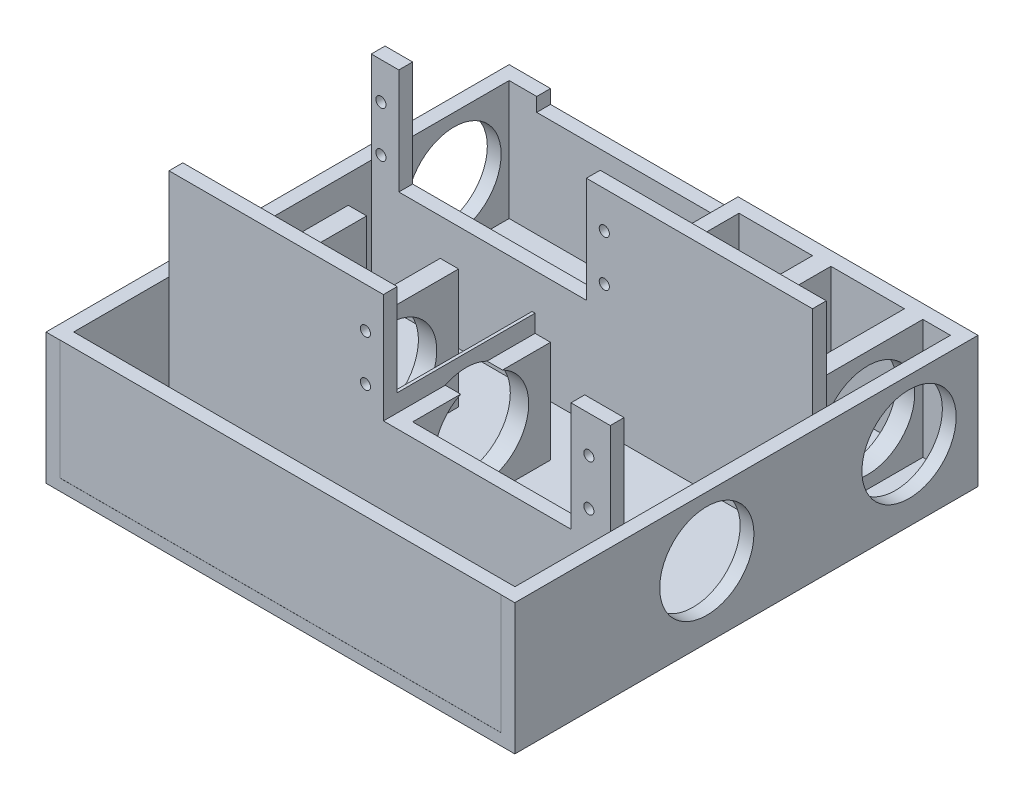
SolidWorks part; units mm, degrees
ref_plane "Front Plane" through (0, 0, 0) normal (0, 0, 1) x (1, 0, 0)
ref_plane "Top Plane" through (0, 0, 0) normal (0, 1, 0) x (1, 0, 0)
ref_plane "Right Plane" through (0, 0, 0) normal (1, 0, 0) x (0, 0, -1)
sketch "Sketch3" plane through (0, 0, 0) normal (0, 1, 0) x (1, 0, 0)
  line L1 (0, 0) -> (-102, 0)
  line L2 (0, 0) -> (0, -136.7612)
  line L3 (0, -136.7612) -> (-102, -136.7612)
  line L4 (-102, 0) -> (-102, -136.7612)
  dimension "D1" = 102
extrude "Boss-Extrude2" add sketch "Sketch3" along normal blind 2.5
sketch "Sketch4" plane through (0, 2.5, 0) normal (0, 1, 0) x (1, 0, 0)
  line L0 (-102, 0) -> (-102, -136.7612) construction
  line L1 (0, 0) -> (-102, 0) construction
  line L2 (-29, 0) -> (-29, -30)
  line L3 (-53, 0) -> (-49, 0)
  line L4 (-53, 0) -> (-53, -30)
  line L5 (-53, -30) -> (-49, -30)
  line L6 (-49, 0) -> (-49, -30)
  line L7 (-33, 0) -> (-33, -30)
  line L8 (-33, 0) -> (-29, 0)
  line L9 (-33, -30) -> (-29, -30)
  line L10 (-9, 0) -> (-9, -30)
  line L11 (-13, 0) -> (-13, -30)
  line L12 (-13, 0) -> (-9, 0)
  line L13 (-13, -30) -> (-9, -30)
  line L14 (-69, -44) -> (-69, -74)
  line L15 (-93, -44) -> (-89, -44)
  line L16 (-93, -44) -> (-93, -74)
  line L17 (-93, -74) -> (-89, -74)
  line L18 (-89, -44) -> (-89, -74)
  line L19 (-73, -44) -> (-73, -74)
  line L20 (-73, -44) -> (-69, -44)
  line L21 (-73, -74) -> (-69, -74)
  line L22 (-49, -44) -> (-49, -74)
  line L23 (-53, -44) -> (-53, -74)
  line L24 (-53, -44) -> (-49, -44)
  line L25 (-53, -74) -> (-49, -74)
  line L26 (0, -136.7612) -> (0, 0) construction
  point P0 (-95, -3)
  point P1 (-15, -3)
  point P7 (-95, -23)
  point P8 (-15, -23)
  dimension "D1" = 80
  dimension "D2" = 7
  dimension "D3" = 3
  dimension "D4" = 3
  dimension "D6" = 30
  dimension "D7" = 4
  dimension "D8" = 9
  dimension "D10" = 16
  dimension "D11" = 16
  dimension "D12" = 9
  dimension "D13" = 9
  dimension "D14" = 16
  dimension "D15" = 16
  dimension "D5" = 2
  dimension "D9" = 2
extrude "Boss-Extrude3" add sketch "Sketch4" along normal blind 26
sketch "Sketch5" plane through (-53, 0, 0) normal (-1, 0, 0) x (0, 0, 1)
  circle A0 centre (15, 15.5) radius 10.25
  dimension "D1" = 20.5
extrude "Cut-Extrude1" cut sketch "Sketch5" against normal through all
sketch "Sketch6" plane through (-93, 0, 0) normal (-1, 0, 0) x (0, 0, 1)
  circle A0 centre (59, 15.5) radius 10.25
  dimension "D1" = 20.5
extrude "Cut-Extrude2" cut sketch "Sketch6" against normal through all
sketch "Sketch7" plane through (0, 2.5, 0) normal (0, 1, 0) x (1, 0, 0)
  line L69 (-3, -3) -> (-9, -3)
  line L70 (-3, -133.7612) -> (-3, -3)
  line L71 (-99, -133.7612) -> (-3, -133.7612)
  line L72 (-53, -3) -> (-99, -3)
  line L73 (-99, -3) -> (-99, -133.7612)
  line L74 (-3, -3) -> (-9, -3)
  line L75 (-3, -133.7612) -> (-3, -3)
  line L76 (-99, -133.7612) -> (-3, -133.7612)
  line L77 (-53, -3) -> (-99, -3)
  line L78 (-99, -3) -> (-99, -133.7612)
  line L85 (-13, -3) -> (-29, -3)
  line L86 (-13, -3) -> (-29, -3)
  line L87 (-33, -3) -> (-33, 0)
  line L88 (-33, -3) -> (-49, -3)
  line L89 (-33, -3) -> (-49, -3)
  line L90 (-33, 0) -> (-49, 0)
  line L91 (-13, -3) -> (-13, 0)
  line L92 (-13, 0) -> (-29, 0)
  line L93 (-29, 0) -> (-29, -3)
  line L94 (-49, 0) -> (-49, -3)
  line L115 (-53, 0) -> (-102, 0)
  line L116 (-102, 0) -> (-102, -136.7612)
  line L117 (-102, -136.7612) -> (0, -136.7612)
  line L118 (0, 0) -> (-9, 0)
  line L119 (0, -136.7612) -> (0, 0)
  line L120 (-53, 0) -> (-102, 0)
  line L121 (-102, 0) -> (-102, -136.7612)
  line L122 (-102, -136.7612) -> (0, -136.7612)
  line L123 (0, 0) -> (-9, 0)
  line L124 (0, -136.7612) -> (0, 0)
  line M21 (-13, -30) -> (-13, 0)
  line M22 (-13, 0) -> (-29, 0)
  line M23 (-29, 0) -> (-29, -30)
  line M25 (-33, -30) -> (-33, 0)
  line M26 (-33, 0) -> (-49, 0)
  line M27 (-49, 0) -> (-49, -30)
  line M29 (-53, -30) -> (-53, 0)
  line M30 (-53, 0) -> (-102, 0)
  line M31 (-102, 0) -> (-102, -136.7612)
  line M32 (-102, -136.7612) -> (0, -136.7612)
  line M33 (0, -136.7612) -> (0, 0)
  line M34 (0, 0) -> (-9, 0)
  line M35 (-9, 0) -> (-9, -30)
  dimension "D1" = 3
  dimension "D2" = 3
  dimension "D3" = 3
  dimension "D5" = 0
extrude "Boss-Extrude5" add sketch "Sketch7" along normal blind 26 contours L89 M25 M26 M27 | L78 L77 L74 L75 L76 M29 M30 M31 M32 M33 M34 M35 | L86 M21 M22 M23 region at (-6, 2.5, 1.2939) region at (-21, 2.5, 1.5) region at (-41, 2.5, 1.5)
sketch "Sketch8" plane through (0, 2.5, 0) normal (0, 1, 0) x (1, 0, 0)
  line L0 (-99, -3) -> (-99, -133.7612) construction
  circle A0 centre (-67, -80) radius 1
  circle A1 centre (-21.28, -80) radius 1
  circle A2 centre (-21.28, -95.24) radius 1
  circle A3 centre (-67, -95.24) radius 1
  point P0 (-67, -80)
  point P2 (-21.28, -80)
  point P7 (-21.28, -95.24)
  point P8 (-67, -95.24)
  dimension "D4" = 2
  dimension "D1" = 32
  dimension "D2" = 6
  dimension "D5" = 2
  dimension "D3" = 2
  dimension "D6" = 2
extrude "Cut-Extrude3" cut sketch "Sketch8" against normal through all
sketch "Sketch9" plane through (0, 0, 0) normal (1, 0, 0) x (0, 0, -1)
  circle A0 centre (-15, 15.5) radius 10.25
  circle A1 centre (-59, 15.5) radius 10.25
  dimension "D1" = 20.5
  dimension "D2" = 20.5
extrude "Cut-Extrude4" cut sketch "Sketch9" against normal through all
sketch "Sketch10" plane through (0, 2.5, 0) normal (0, 1, 0) x (1, 0, 0)
  line L0 (-3, -133.7612) -> (-3, -3) construction
  line L1 (-3, -30) -> (-99, -30)
  line L2 (-3, -30) -> (-3, -33)
  line L3 (-3, -33) -> (-99, -33)
  line L4 (-99, -30) -> (-99, -33)
  line L5 (-99, -3) -> (-99, -133.7612) construction
  line L6 (-3, -74) -> (-99, -74)
  line L7 (-99, -77) -> (-3, -77)
  line L8 (-3, -74) -> (-3, -77)
  line L9 (-99, -74) -> (-99, -77)
  point P16 (-3, -77)
  point P19 (-99, -77)
  dimension "D1" = 3
  dimension "D2" = 0
extrude "Boss-Extrude6" add sketch "Sketch10" along normal blind 46
sketch "Sketch13" plane through (0, 2.5, 0) normal (0, 1, 0) x (1, 0, 0)
  line L0 (-3, -133.7612) -> (-3, -77) construction
  line L1 (-3, -97.74) -> (-99, -97.74)
  line L2 (-3, -97.74) -> (-3, -100.74)
  line L3 (-3, -100.74) -> (-99, -100.74)
  line L4 (-99, -97.74) -> (-99, -100.74)
  line L5 (-99, -77) -> (-99, -133.7612) construction
  circle A0 centre (-21.28, -95.24) radius 1 construction
  dimension "D2" = 2.5
  dimension "D1" = 3
extrude "Boss-Extrude7" add sketch "Sketch13" along normal blind 26
sketch "Sketch14" plane through (0, 0, 0) normal (0, -1, 0) x (1, 0, 0)
  line L1 (-102, 0) -> (-102, 136.7612) construction
  line L2 (0, 136.7612) -> (-102, 136.7612)
  line L3 (0, 136.7612) -> (0, 100.7612)
  line L4 (0, 100.7612) -> (-102, 100.7612)
  line L5 (-102, 136.7612) -> (-102, 100.7612)
  dimension "D1" = 36
extrude "Cut-Extrude7" cut sketch "Sketch14" against normal through all
sketch "Sketch15" plane through (0, 0, 33) normal (0, 0, 1) x (1, 0, 0)
  line L0 (-93, 48.5) -> (-93, 25.5)
  line L1 (-93, 25.5) -> (-52.2, 25.5)
  line L2 (-52.2, 48.5) -> (-52.2, 25.5)
  line L3 (-99, 48.5) -> (-3, 48.5) construction
  circle A0 centre (-96.9, 30.5) radius 1.1036
  circle A1 centre (-48.3, 30.5) radius 1.1036
  circle A2 centre (-48.3, 40.5) radius 1.1036
  circle A3 centre (-96.9, 40.5) radius 1.1036
  point P6 (-72.6, 25.5)
  point P13 (-95.0561, 46.2876)
  point P17 (0, 0)
  point P18 (0, 0)
  line M6 (-3, 48.5) -> (-99, 48.5)
  dimension "D13" = 0
  dimension "D1" = 24.3
  dimension "D2" = 8
  dimension "D3" = 24.3
  dimension "D4" = 0
  dimension "D5" = 6
  dimension "D6" = 8
  dimension "D7" = 40.8
  dimension "D8" = 10
  dimension "D9" = 23
  dimension "D10" = 23
  dimension "D11" = 10
  dimension "D12" = 0
extrude "Cut-Extrude8" cut sketch "Sketch15" against normal up to next contours L2 L0 L1 M6 | A3 | A0 | A1 | A2 region at (-72.6, 37, 33) region at (-96.9, 30.5, 33) region at (-48.3, 30.5, 33) region at (-48.3, 40.5, 33) region at (-96.9, 40.5, 33)
sketch "Sketch16" plane through (0, 0, 77) normal (0, 0, 1) x (1, 0, 0)
  line L0 (-52.3579, 24.6856) -> (-11.5579, 24.6856)
  line L1 (-11.5579, 48.5) -> (-11.5579, 24.6856)
  line L2 (-99, 48.5) -> (-3, 48.5) construction
  line L3 (-52.3579, 24.6856) -> (-52.3579, 48.5)
  circle A0 centre (-56.2579, 29.6856) radius 1.1036
  circle A1 centre (-7.6579, 30.5) radius 1.1036
  circle A2 centre (-7.6579, 40.5) radius 1.1036
  circle A3 centre (-56.2579, 39.6856) radius 1.1036
  point P5 (-31.9579, 24.6856)
  line M4 (-3, 48.5) -> (-99, 48.5)
  dimension "D1" = 24.3
  dimension "D2" = 24.3
  dimension "D3" = 10
  dimension "D4" = 0
  dimension "D5" = 0
  dimension "D6" = 8
  dimension "D7" = 10
  dimension "D8" = 24.3
extrude "Cut-Extrude9" cut sketch "Sketch16" against normal up to next contours L3 L0 L1 M4 | A3 | A2 | A1 | A0 region at (-31.9579, 36.5928, 77) region at (-7.6579, 30.5, 77) region at (-7.6579, 40.5, 77) region at (-56.2579, 39.6856, 77)
